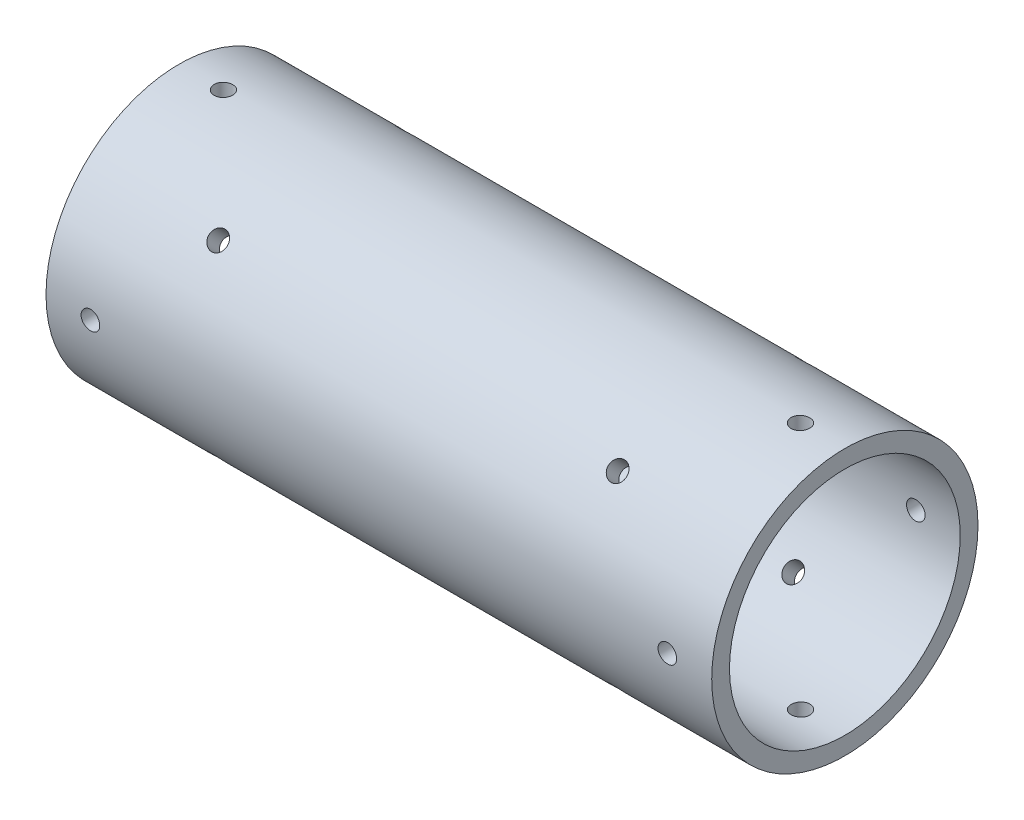
SolidWorks part; units mm, degrees
material "Д16Т  ГОСТ 13616-97"
ref_plane "Спереди" through (0, 0, 0) normal (0, 0, 1) x (1, 0, 0)
ref_plane "Сверху" through (0, 0, 0) normal (0, 1, 0) x (1, 0, 0)
ref_plane "Справа" through (0, 0, 0) normal (1, 0, 0) x (0, 0, -1)
sketch "Эскиз1" plane through (0, 0, 0) normal (1, 0, 0) x (0, 0, -1)
  circle A0 centre (0, 0) radius 30
  circle A1 centre (0, 0) radius 26
  dimension "D1" = 60
  dimension "D2" = 4
extrude "Бобышка-Вытянуть1" add sketch "Эскиз1" along normal blind 150
sketch "Эскиз2" plane through (0, 0, 0) normal (0, 1, 0) x (1, 0, 0)
  line L0 (0, 30) -> (0, -30) construction
  line L1 (150, -30) -> (150, 30) construction
  circle A0 centre (10, 0) radius 2.1
  circle A1 centre (140, 0) radius 2.1
  dimension "D1" = 4.2
  dimension "D2" = 10
  dimension "D3" = 10
extrude "Вырез-Вытянуть1" cut sketch "Эскиз2" against normal through all both and the other way through all
ref_axis "Ось1" through (150, 0, 0) along (-1, 0, 0)
ref_plane "Плоскость1" through (0, 0, 0) normal (0, 0.7071, -0.7071) x (-1, 0, 0)
sketch "Эскиз3" plane through (0, 0, 0) normal (0, 0.7071, -0.7071) x (-1, 0, 0)
  line L0 (-150, 30) -> (-150, -30) construction
  line L1 (0, -30) -> (0, 30) construction
  circle A0 centre (-120, 0) radius 2.1
  circle A1 centre (-30, 0) radius 2.1
  dimension "D1" = 4.2
  dimension "D3" = 30
  dimension "D2" = 30
extrude "Вырез-Вытянуть2" cut sketch "Эскиз3" against normal through all both and the other way through all
pattern_circular "Круговой массив1" count 2 every 90 about axis through (150, 0, 0) along (-1, 0, 0) of "Вырез-Вытянуть2", "Вырез-Вытянуть1"
